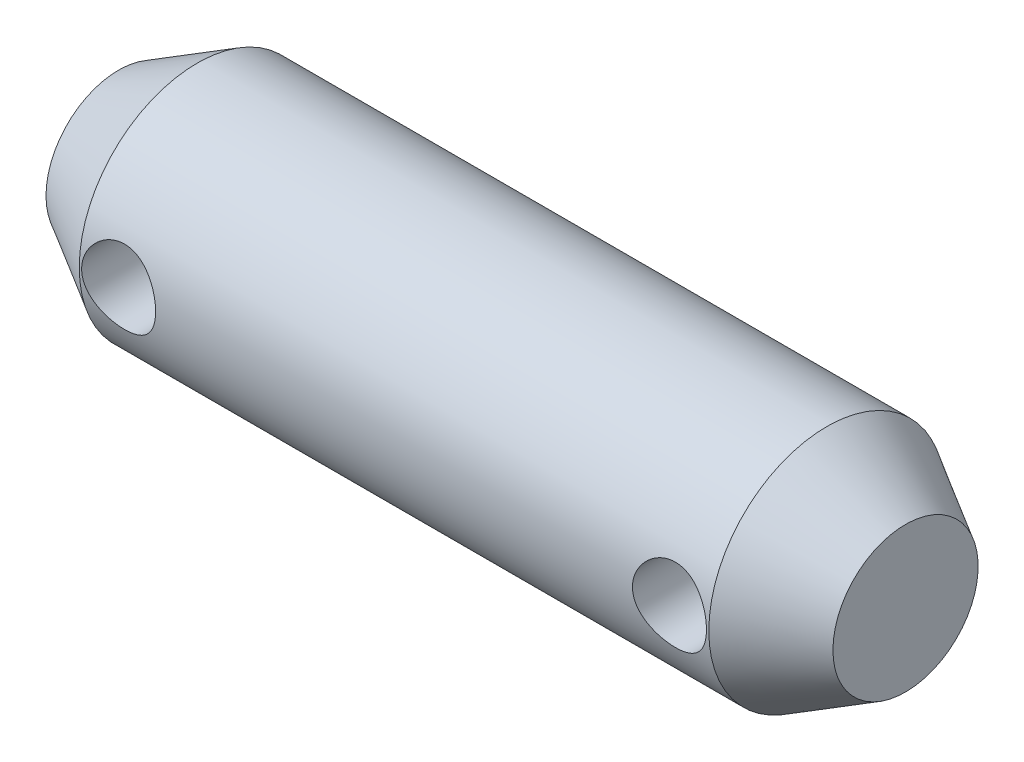
SolidWorks part; units mm, degrees
ref_plane "Front" through (0, 0, 0) normal (0, 0, 1) x (1, 0, 0)
ref_plane "Top" through (0, 0, 0) normal (0, 1, 0) x (1, 0, 0)
ref_plane "Right" through (0, 0, 0) normal (1, 0, 0) x (0, 0, -1)
sketch "Sketch1" plane through (0, 0, 0) normal (0, 0, 1) x (1, 0, 0)
  line L0 (10, 0) -> (10, 0.9226)
  line L1 (10, 0.9226) -> (9, 1.5)
  line L2 (9, 1.5) -> (1, 1.5)
  line L3 (1, 1.5) -> (0, 0.9226)
  line L4 (0, 0.9226) -> (0, 0)
  line L5 (0, 0) -> (10, 0)
  line L6 (-13.7358, 0) -> (5.379, 0) construction
  dimension "D3" = 30
  dimension "D4" = 30
revolve "Base-Revolve" add sketch "Sketch1" angle 360 about L6
sketch "Sketch2" plane through (0, 0, 0) normal (0, 0, 1) x (1, 0, 0)
  line L2 (0, 0.9226) -> (0, -0.9226) construction
  circle A0 centre (8.5, 0) radius 0.47
  circle A1 centre (1.5, 0) radius 0.47
  dimension "d1" = 0.94
  dimension "le" = 1.5
  dimension "lh" = 7
extrude "Hole" cut sketch "Sketch2" against normal through all and the other way through all
equation "\"c1@Sketch1\" = \"c@Sketch1\""
